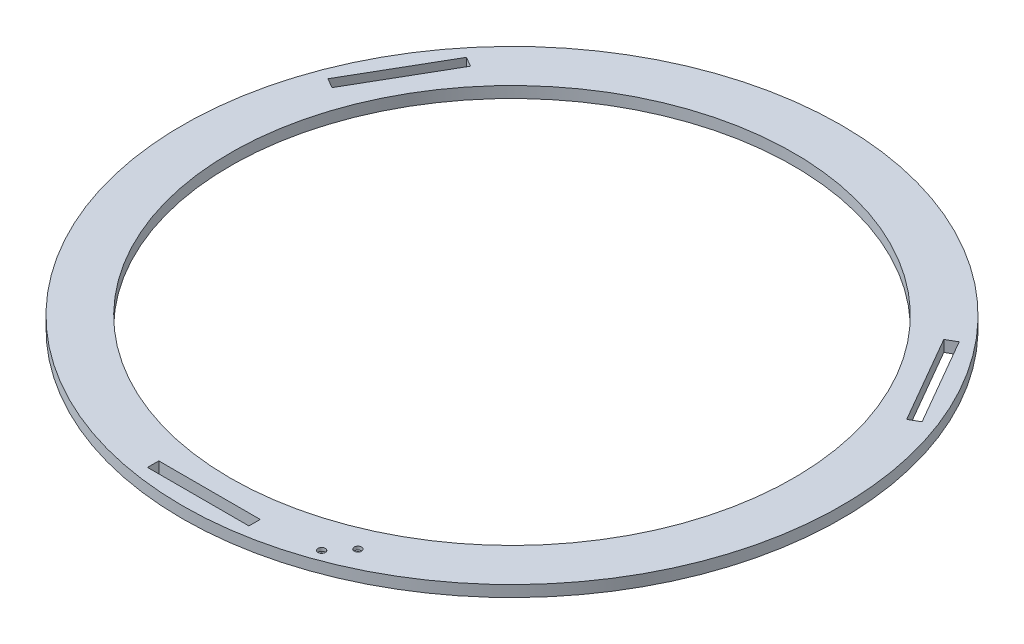
SolidWorks part; units mm, degrees
ref_plane "Front Plane" through (0, 0, 0) normal (0, 0, 1) x (1, 0, 0)
ref_plane "Top Plane" through (0, 0, 0) normal (0, 1, 0) x (1, 0, 0)
ref_plane "Right Plane" through (0, 0, 0) normal (1, 0, 0) x (0, 0, -1)
sketch "Sketch1" plane through (0, 0, 0) normal (0, 1, 0) x (1, 0, 0)
  circle A0 centre (0, 0) radius 250
  circle A1 centre (0, 0) radius 292.5
  dimension "D1" = 500
  dimension "D2" = 585
extrude "Boss-Extrude1" add sketch "Sketch1" along normal blind 10
sketch "Sketch2" plane through (0, 10, 0) normal (0, 1, 0) x (1, 0, 0)
  line L0 (-45, -278.5) -> (45, -278.5)
  line L1 (45, -278.5) -> (45, -268.5)
  line L2 (45, -268.5) -> (-45, -268.5)
  line L3 (-45, -268.5) -> (-45, -278.5)
  line L4 (0, -268.5) -> (0, 0) construction
  line L5 (0, -268.5) -> (0, -291) construction
  circle A0 centre (0, 0) radius 291 construction
  dimension "D4" = 582
  dimension "D1" = 10
  dimension "D2" = 90
  dimension "D3" = 12.5
extrude "Cut-Extrude1" cut sketch "Sketch2" against normal blind 10
pattern_circular "CirPattern1" count 3 over 360 about axis through (0, 10, 0) along (0, 1, 0) of "Cut-Extrude1"
hole_wizard "CBORE for M3 SHCS1" positions "Sketch5" profile "Sketch6" counterbore size "M3" standard "ANSI Metric" end condition through all
sketch "Sketch5" plane through (0, 10, 0) normal (0, 1, 0) x (1, 0, 0)
  point P0 (111.1755, -247.9405)
  point P2 (96.082, -265.0397)
sketch "Sketch6" plane through (111.1755, 10, 247.9405) normal (1, 0, 0) x (0, 0, 1)
  line L0 (0, 0) -> (0, 10)
  line L1 (0, 10) -> (1.7, 10)
  line L2 (1.7, 10) -> (1.7, 3)
  line L3 (1.7, 3) -> (3.25, 3)
  line L4 (3.25, 3) -> (3.25, 0)
  line L5 (3.25, 0) -> (0, 0)
  line L6 (0, -6.35) -> (0, 107.95) construction
  dimension "Thru Hole Dia." = 3.4
  dimension "Thru Hole Depth" = 10
  dimension "C'Bore Dia." = 6.5
  dimension "C'Bore Depth" = 3
